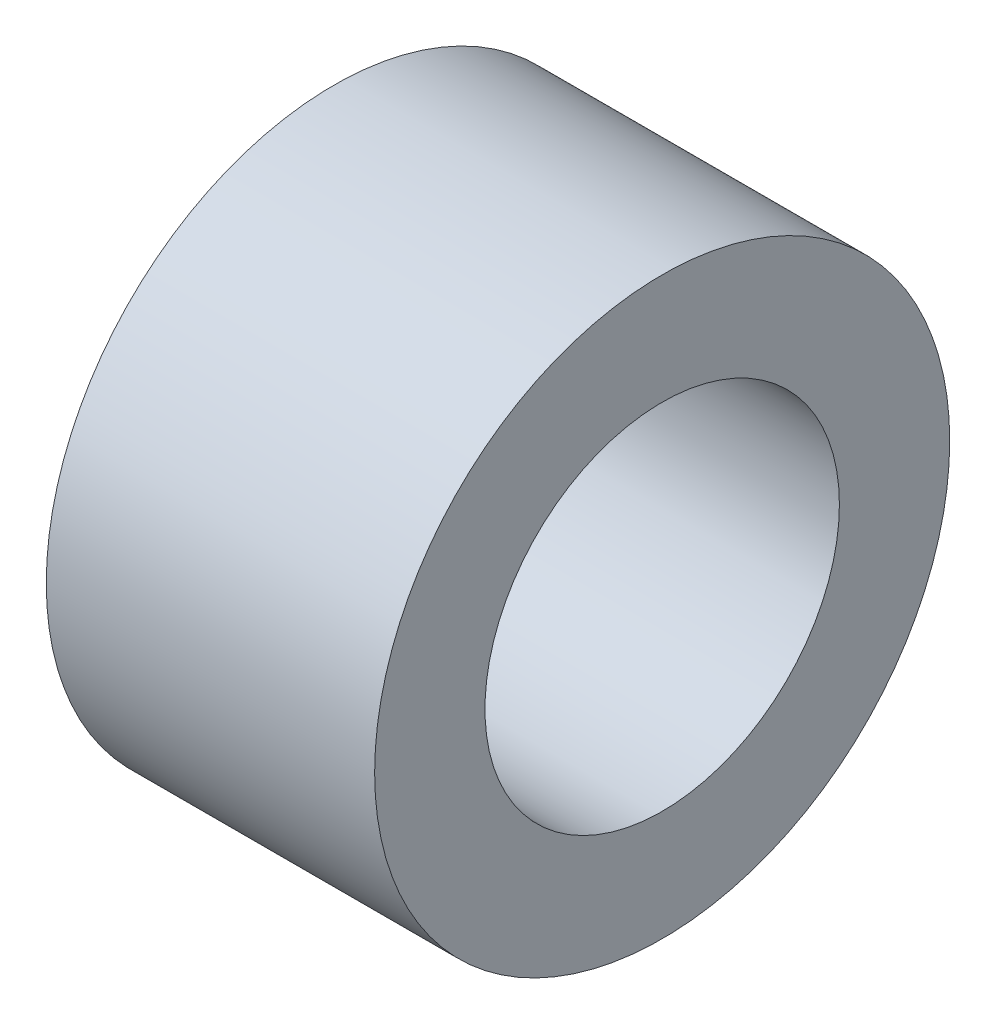
SolidWorks part; units mm, degrees
material "Nylon 101"
ref_plane "Front Plane" through (0, 0, 0) normal (0, 0, 1) x (1, 0, 0)
ref_plane "Top Plane" through (0, 0, 0) normal (0, 1, 0) x (1, 0, 0)
ref_plane "Right Plane" through (0, 0, 0) normal (1, 0, 0) x (0, 0, -1)
sketch "Sketch1" plane through (0, 0, 0) normal (1, 0, 0) x (0, 0, -1)
  circle A0 centre (0, 0) radius 10.2
  circle A1 centre (0, 0) radius 11.9011
  dimension "D1" = 20.4
  dimension "D2" = 23.8022
extrude "Boss-Extrude1" add sketch "Sketch1" along normal blind 1
sketch "Sketch2" plane through (1, 0, 0) normal (1, 0, 0) x (0, 0, -1)
  circle A0 centre (0, 0) radius 16.55
  circle A1 centre (0, 0) radius 10.2 construction
  circle A2 centre (0, 0) radius 10.2
  dimension "D1" = 6.35
extrude "Boss-Extrude2" add sketch "Sketch2" along normal blind 18.9
equation "\"D2@Sketch1\"=11.9011mm*2"
equation "\"D1@Boss-Extrude1\"=1mm"
equation "\"D1@Boss-Extrude2\"=18.9mm"
